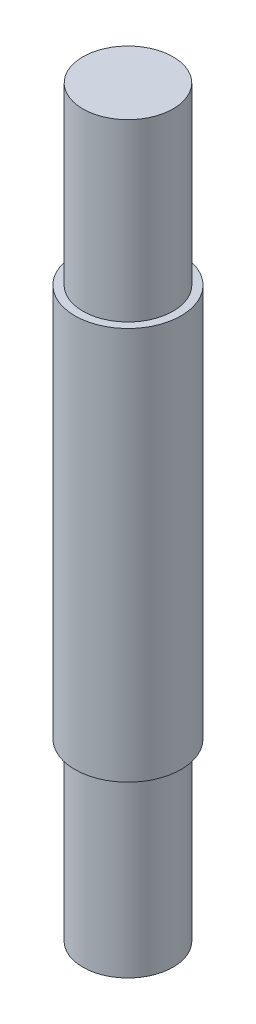
SolidWorks part; units mm, degrees
ref_plane "Front Plane" through (0, 0, 0) normal (0, 0, 1) x (1, 0, 0)
ref_plane "Top Plane" through (0, 0, 0) normal (0, 1, 0) x (1, 0, 0)
ref_plane "Right Plane" through (0, 0, 0) normal (1, 0, 0) x (0, 0, -1)
sketch "Sketch1" plane through (0, 0, 0) normal (0, 1, 0) x (1, 0, 0)
  circle A0 centre (0, 0) radius 8.5
  dimension "D1" = 17
extrude "Boss-Extrude1" add sketch "Sketch1" along normal blind 70 and the other way blind 70
sketch "Sketch2" plane through (0, 0, 0) normal (0, 1, 0) x (1, 0, 0)
  circle A0 centre (0, 0) radius 10
  dimension "D1" = 20
extrude "Boss-Extrude2" add sketch "Sketch2" along normal blind 37 and the other way blind 37
